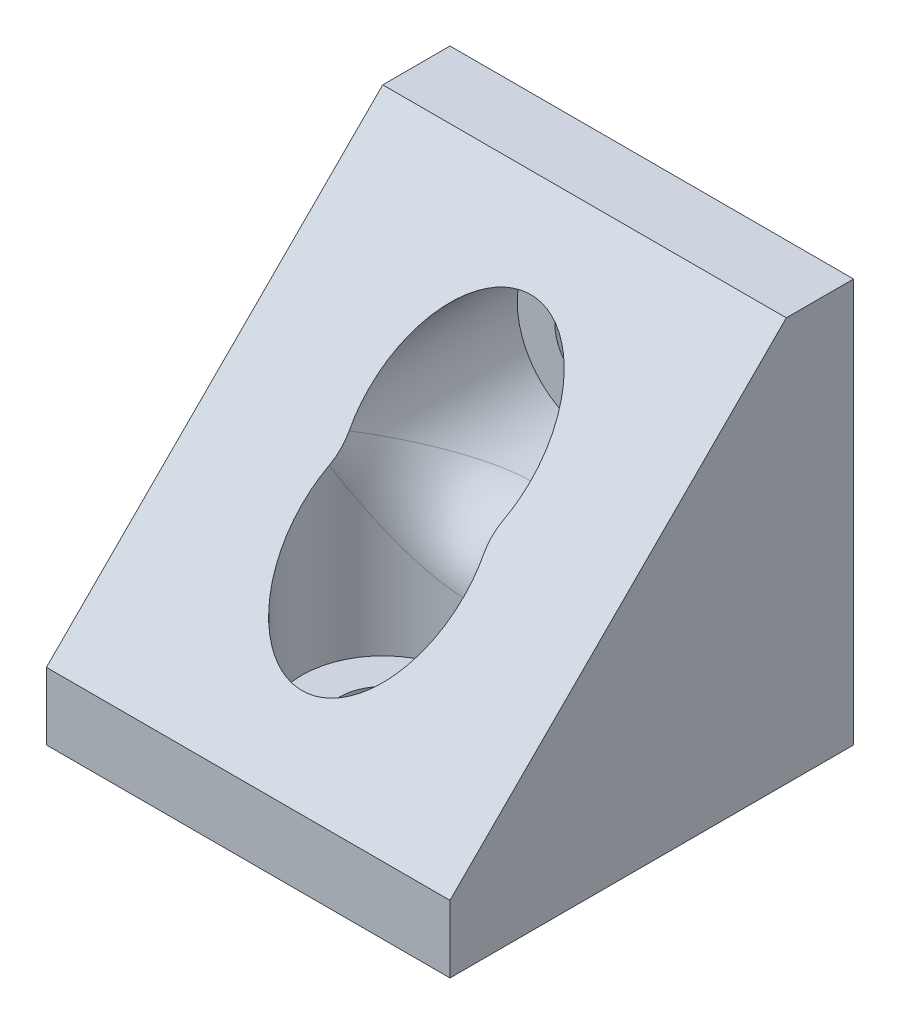
SolidWorks part; units mm, degrees
ref_plane "Front Plane" through (0, 0, 0) normal (1, 0, 0) x (0, 1, 0)
ref_plane "Top Plane" through (0, 0, 0) normal (0, 0, 1) x (0, 1, 0)
ref_plane "Right Plane" through (0, 0, 0) normal (0, 1, 0) x (-1, 0, 0)
sketch "Sketch1" plane through (0, 0, 0) normal (1, 0, 0) x (0, 1, 0)
  line L0 (0, 0) -> (30, 0)
  line L1 (30, 0) -> (30, 5)
  line L2 (30, 5) -> (17.5, 17.5)
  line L3 (17.5, 17.5) -> (0, 0)
  point P5 (70.1699, 20.7668)
  point P6 (13.4073, 13.4073)
  dimension "D1" = 45
  dimension "D2" = 5
  dimension "D3" = 30
extrude "Boss-Extrude1" add sketch "Sketch1" along normal blind 30 contours L3 L0 L1 L2
sketch "Sketch2" plane through (0, 0, 0) normal (0, 0, -1) x (1, 0, 0)
  line L0 (15, -20) -> (15, -30)
  line L1 (30, -30) -> (0, -30) construction
  circle A0 centre (15, -20) radius 3.2
  circle A1 centre (15, -20) radius 6
  dimension "D1" = 6.4
  dimension "D3" = 12
  dimension "D2" = 10
extrude "Cut-Extrude1" cut sketch "Sketch2" against normal through all contours A0
extrude "Cut-Extrude2" cut sketch "Sketch2<3>" against normal through all from offset 4 contours A1 A0 region at (10.8774, 15.8774, 0) offset against normal yes
sketch "Sketch2<3>" plane through (0, 0, 0) normal (0, 0, -1) x (1, 0, 0) same geometry as "Sketch2"
ref_plane "Plane1" through (0, 0, 0) normal (0, -0.7071, 0.7071) x (1, 0, 0)
mirror "Mirror1" about plane through (30, 17.5, 17.5) normal (0, 0.7071, -0.7071) of bodies 103
fillet "Fillet1" radius 5 1 edges at (15, 14, 14)
